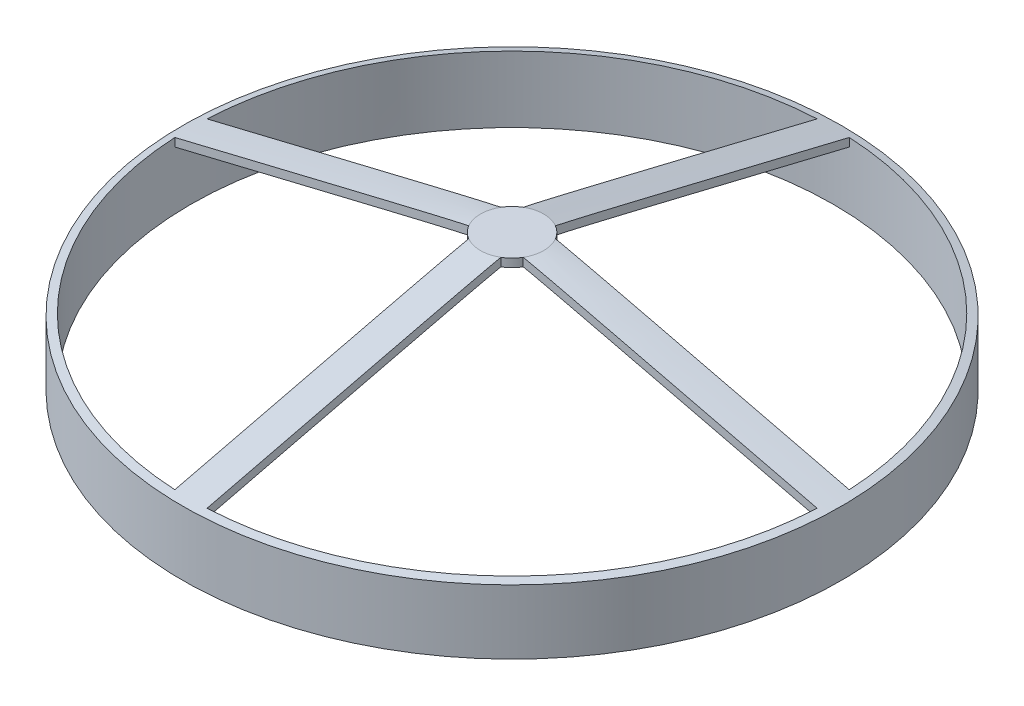
SolidWorks part; units mm, degrees
ref_plane "Front Plane" through (0, 0, 0) normal (0, 0, 1) x (1, 0, 0)
ref_plane "Top Plane" through (0, 0, 0) normal (0, 1, 0) x (1, 0, 0)
ref_plane "Right Plane" through (0, 0, 0) normal (1, 0, 0) x (0, 0, -1)
sketch "Sketch1" plane through (0, 0, 0) normal (0, 0, 1) x (1, 0, 0)
  line L0 (0, 0) -> (0, 53.975)
  line L1 (0, 53.975) -> (12.5, 53.975)
  line L2 (12.5, 53.975) -> (130.175, 25.4)
  line L3 (130.175, 25.4) -> (130.175, 0)
  line L4 (130.175, 0) -> (0, 0)
  dimension "D1" = 12.5
  dimension "D2" = 25.4
  dimension "D3" = 28.575
  dimension "D4" = 130.175
revolve "Revolve1" add sketch "Sketch1" angle 360 about L0 other way angle 360
shell "Shell1" thickness 3.175 removed face at (0, 0, -130.175)
sketch "Sketch2" plane through (0, 53.975, 0) normal (0, 1, 0) x (1, 0, 0)
  line L1 (-6.35, 10.767) -> (-6.35, 126.8412)
  line L3 (6.35, 126.8412) -> (6.35, 10.767)
  line L4 (0, 0) -> (0, 196.1282) construction
  line L5 (10.767, 6.35) -> (126.8412, 6.35)
  line L6 (126.8412, -6.35) -> (10.767, -6.35)
  line L7 (6.35, -10.767) -> (6.35, -126.8412)
  line L8 (-6.35, -126.8412) -> (-6.35, -10.767)
  line L9 (-10.767, -6.35) -> (-126.8412, -6.35)
  line L10 (-126.8412, 6.35) -> (-10.767, 6.35)
  circle A0 centre (0, 0) radius 12.5
  circle A1 centre (0, 0) radius 127
  point P24 (0, 0)
  circle M7 centre (0, 0) radius 12.5
  dimension "D1" = 254
  dimension "D2" = 25
  dimension "D3" = 12.7
  dimension "D4" = 6.35
  dimension "D5" = 4
extrude "Cut-Extrude1" cut sketch "Sketch2" against normal through all contours L1 A1 L10 M7 | L5 A1 L3 M7 | L7 A1 L6 M7 | L9 A1 L8 M7 region at (-56.7561, 53.975, -56.7561) region at (56.7561, 53.975, -56.7561) region at (-56.7561, 53.975, 56.7561) region at (56.7561, 53.975, 56.7561)
